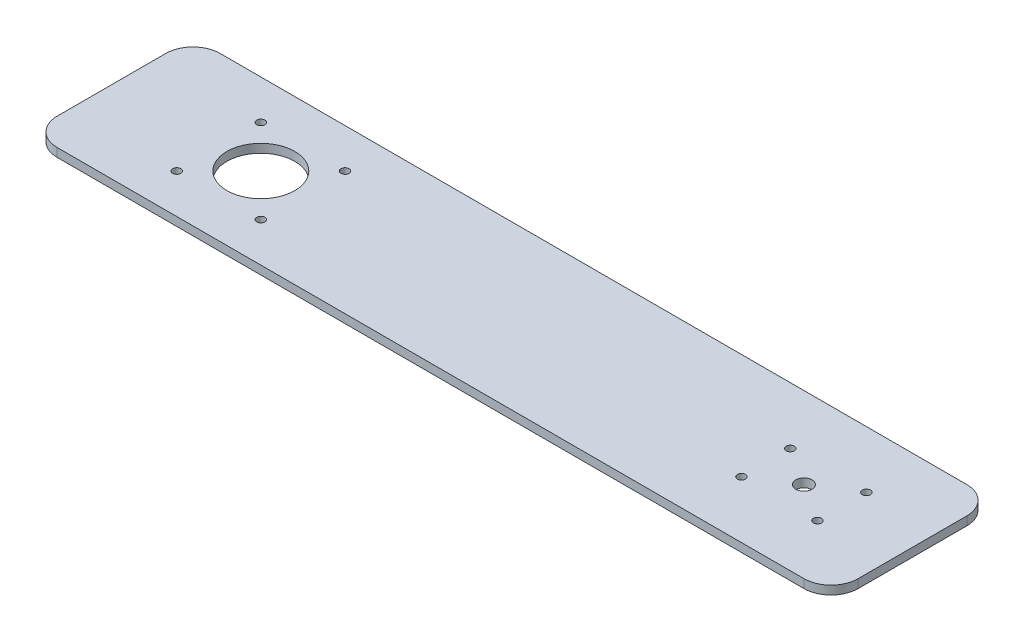
SolidWorks part; units mm, degrees
ref_plane "Front Plane" through (0, 0, 0) normal (0, 0, 1) x (1, 0, 0)
ref_plane "Top Plane" through (0, 0, 0) normal (0, 1, 0) x (1, 0, 0)
ref_plane "Right Plane" through (0, 0, 0) normal (1, 0, 0) x (0, 0, -1)
sketch "Sketch1" plane through (0, 0, 0) normal (0, 1, 0) x (1, 0, 0)
  line L0 (-55, 0) -> (0, 0) construction
  line L1 (-55, 30) -> (240, 30)
  line L2 (-55, 30) -> (-55, -30)
  line L3 (-55, -30) -> (240, -30)
  line L4 (240, 30) -> (240, -30)
  point P7 (200, 0)
  dimension "D1" = 60
  dimension "D2" = 55
  dimension "D3" = 200
  dimension "D4" = 40
extrude "Boss-Extrude1" add sketch "Sketch1" along normal blind 3.175
fillet "Fillet1" radius 10 4 edges at (-55, 1.5875, 30) (-55, 1.5875, -30) (240, 1.5875, 30) (240, 1.5875, -30)
hole_wizard "Ø3.0mm Dowel Hole1" positions "Sketch3" profile "Sketch5" hole size "Ø3.0" standard "DIN" end condition up to next
sketch "Sketch3" plane through (0, 3.175, 0) normal (0, 1, 0) x (1, 0, 0)
  point P0 (-15.5, 15.5)
  point P29 (15.5, 15.5)
  point P30 (15.5, -15.5)
  point P31 (-15.5, -15.5)
  dimension "D1" = 15.5
  dimension "D2" = 15.5
  dimension "D5" = 31
  dimension "D6" = 31
  dimension "D3" = 2
  dimension "D4" = 2
sketch "Sketch5" plane through (-15.5, 3.175, -15.5) normal (1, 0, 0) x (0, 0, 1)
  line L0 (0, 0) -> (0, 3.175)
  line L1 (0, 3.175) -> (1.5, 3.175)
  line L2 (1.5, 3.175) -> (1.5, 0)
  line L5 (1.5, 0) -> (0, 0)
  line L11 (0, -6.35) -> (0, 107.95) construction
  dimension "Thru Hole Dia." = 3
  dimension "Thru Hole Depth" = 3.175
sketch "Sketch6" plane through (0, 3.175, 0) normal (0, 1, 0) x (1, 0, 0)
  circle A0 centre (0, 0) radius 12.5
  dimension "D1" = 25
extrude "Cut-Extrude1" cut sketch "Sketch6" against normal through all
hole_wizard "Ø6.0mm Dowel Hole1" positions "Sketch7" profile "Sketch8" hole size "Ø6.0" standard "DIN" end condition up to next
sketch "Sketch7" plane through (0, 3.175, 0) normal (0, 1, 0) x (1, 0, 0)
  point P0 (200, 0)
  dimension "D1" = 200
sketch "Sketch8" plane through (200, 3.175, 0) normal (1, 0, 0) x (0, 0, 1)
  line L0 (0, 0) -> (0, 3.175)
  line L1 (0, 3.175) -> (3, 3.175)
  line L2 (3, 3.175) -> (3, 0)
  line L5 (3, 0) -> (0, 0)
  line L11 (0, -6.35) -> (0, 107.95) construction
  dimension "Thru Hole Dia." = 6
  dimension "Thru Hole Depth" = 3.175
hole_wizard "Ø3.0mm Dowel Hole2" positions "Sketch10" profile "Sketch11" hole size "Ø3.0" standard "ANSI Metric" end condition up to next
sketch "Sketch10" plane through (0, 0, 0) normal (0, -1, 0) x (-1, 0, 0)
  line L0 (-214, 9) -> (-186, 9) construction
  circle A0 centre (-200, 0) radius 3 construction
  point P0 (-214, 9)
  point P7 (-186, 9)
  point P8 (-186, -9)
  point P9 (-214, -9)
  point P14 (0, 0)
  point P15 (0, 0)
  point P16 (0, 0)
  dimension "D4" = 14
  dimension "D5" = 9
  dimension "D3" = 28
  dimension "D6" = 18
  dimension "D1" = 2
  dimension "D2" = 2
sketch "Sketch11" plane through (214, 0, -9) normal (1, 0, 0) x (0, 0, -1)
  line L0 (0, 0) -> (0, 3.175)
  line L1 (0, 3.175) -> (1.5, 3.175)
  line L2 (1.5, 3.175) -> (1.5, 0)
  line L5 (1.5, 0) -> (0, 0)
  line L11 (0, -6.35) -> (0, 107.95) construction
  dimension "Thru Hole Dia." = 3
  dimension "Thru Hole Depth" = 3.175
equation "\"Pivot to Pivot Dist\"= 200"
equation "\"D3@Sketch1\"=\"Pivot to Pivot Dist\""
equation "\"D1@Sketch7\"=\"Pivot to Pivot Dist\""
